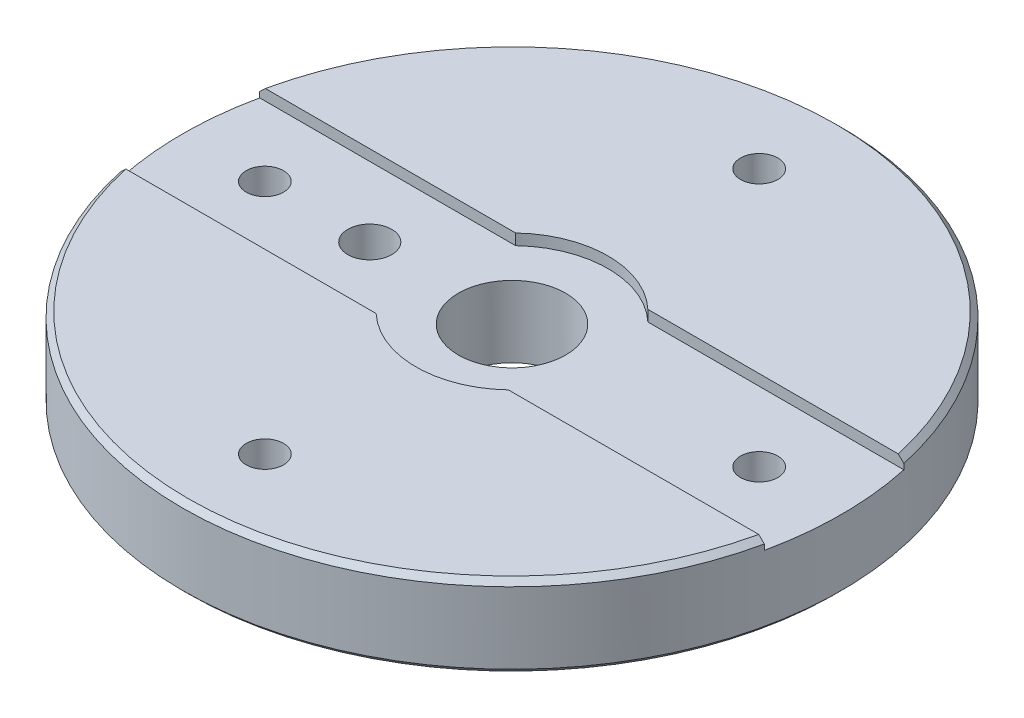
SolidWorks part; units mm, degrees
material "Plain Carbon Steel"
ref_plane "Front Plane" through (0, 0, 0) normal (0, 0, 1) x (1, 0, 0)
ref_plane "Top Plane" through (0, 0, 0) normal (0, 1, 0) x (1, 0, 0)
ref_plane "Right Plane" through (0, 0, 0) normal (1, 0, 0) x (0, 0, -1)
sketch "Sketch1" plane through (0, 0, 0) normal (0, 1, 0) x (1, 0, 0)
  circle A0 centre (0, 0) radius 60
  circle A1 centre (0, 0) radius 9.765
  dimension "D1" = 120
  dimension "D2" = 19.53
extrude "Boss-Extrude1" add sketch "Sketch1" against normal blind 15
chamfer "Chamfer1" distance 1 angle 45 2 edges at (0, -15, 60) (0, 0, 60)
hole_wizard "M8 Tapped Hole1" positions "Sketch6" profile "Sketch3" tap size "M8" standard "ISO" end condition through all
sketch "Sketch6" plane through (0, 0, 0) normal (0, 1, 0) x (1, 0, 0)
  line L0 (0, -45) -> (0, 45) construction
  line L2 (-45, 0) -> (45, 0) construction
  circle A0 centre (0, 0) radius 45
  point P10 (0, -45)
  point P11 (0, 45)
  point P14 (-45, 0)
  point P15 (45, 0)
  point P59 (0, 45)
  point P61 (45, 0)
  point P63 (0, -45)
  point P65 (-45, 0)
  dimension "D1" = 90
sketch "Sketch3" plane through (-45, 0, 0) normal (1, 0, 0) x (0, 0, 1)
  line L0 (0, 0) -> (0, 15)
  line L1 (0, 15) -> (3.4, 15)
  line L2 (3.4, 15) -> (3.4, 0)
  line L5 (3.4, 0) -> (0, 0)
  line L11 (0, -6.35) -> (0, 107.95) construction
  dimension "Thru Tap Drill Dia." = 6.8
  dimension "Thru Tap Drill Depth" = 15
cosmetic thread "Hole Thread1" parameters "D2"=8
cosmetic thread "Hole Thread2" parameters "D2"=8
cosmetic thread "Hole Thread3" parameters "D2"=8
cosmetic thread "Hole Thread4" parameters "D2"=8
sketch "Sketch5" plane through (0, -15, 0) normal (0, -1, 0) x (1, 0, 0)
  line L0 (0, 0) -> (0, 45) construction
  circle A0 centre (0, 0) radius 45 construction
  circle A1 centre (0, 45) radius 10
  dimension "D1" = 0
  dimension "D2" = 20
extrude "Cut-Extrude1" cut sketch "Sketch5" against normal blind 3 contours A1
pattern_circular "CirPattern1" count 12 every 30 about axis through (0, -15, 0) along (0, -1, 0) of "Cut-Extrude1"
sketch "Sketch7" plane through (0, 0, 0) normal (0, 1, 0) x (1, 0, 0)
  line L1 (-60, -12.7) -> (60, -12.7)
  line L2 (-60, -12.7) -> (-60, 12.7)
  line L3 (-60, 12.7) -> (60, 12.7)
  line L4 (60, -12.7) -> (60, 12.7)
  line L5 (-60, -12.7) -> (60, 12.7) construction
  line L6 (-60, 12.7) -> (60, -12.7) construction
  circle A0 centre (0, 0) radius 60 construction
  point P0 (0, 0)
  dimension "D1" = 25.4
extrude "Cut-Extrude2" cut sketch "Sketch7" against normal blind 2 contours L3 L4 L1 L2
sketch "Sketch8" plane through (0, 0, 0) normal (0, 1, 0) x (1, 0, 0)
  circle A0 centre (-25.9, 0) radius 4
  dimension "D1" = 25.9
  dimension "D2" = 8
extrude "Cut-Extrude3" cut sketch "Sketch8" against normal up to next and the other way through all
sketch "Sketch9" plane through (0, 0, 0) normal (0, 1, 0) x (1, 0, 0)
  circle A0 centre (0, 0) radius 17.5
  dimension "D1" = 35
extrude "Cut-Extrude4" cut sketch "Sketch9" against normal up to surface (2 mm away) up to face at (-25.9, -2, -4)
